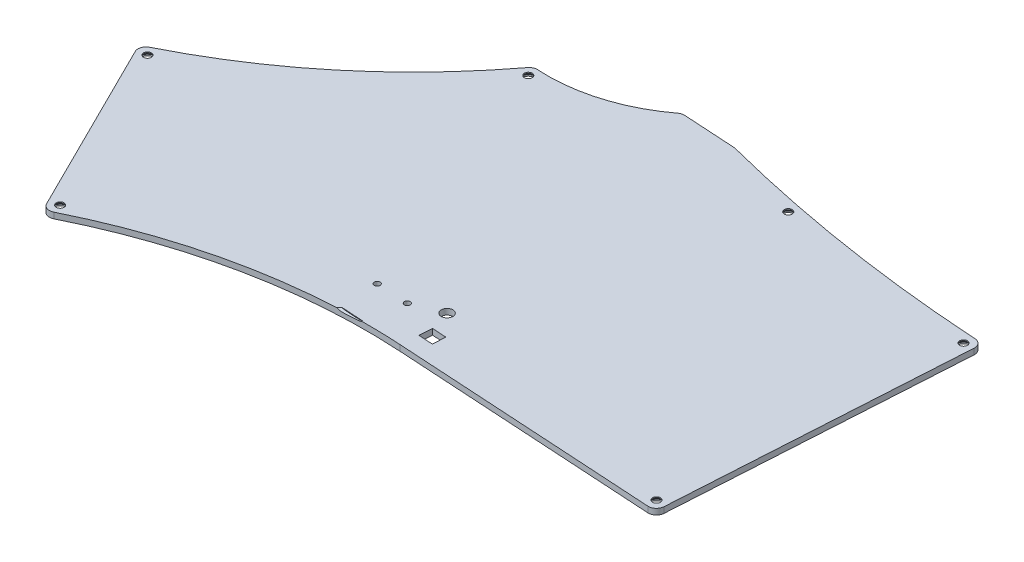
SolidWorks part; units mm, degrees
ref_plane "Front Plane" through (0, 0, 0) normal (0, 0, 1) x (1, 0, 0)
ref_plane "Top Plane" through (0, 0, 0) normal (0, 1, 0) x (1, 0, 0)
ref_plane "Right Plane" through (0, 0, 0) normal (1, 0, 0) x (0, 0, -1)
sketch "Main_line" plane through (0, 0, 0) normal (0, 1, 0) x (1, 0, 0)
  line L0 (47.5657, -117.8094) -> (51.8578, -118.0699) construction
  line L9 (47.2541, -117.9909) -> (52.1451, -118.2877) construction
  line L10 (47.2541, -117.9909) -> (47.5207, -113.5989) construction
  line L11 (47.5207, -113.5989) -> (52.4117, -113.8958) construction
  line L12 (52.1451, -118.2877) -> (52.4117, -113.8958) construction
  line L13 (47.2541, -117.9909) -> (52.4117, -113.8958) construction
  line L14 (47.5207, -113.5989) -> (52.1451, -118.2877) construction
  line L15 (51.9637, -117.9762) -> (52.1939, -114.1831) construction
  line L16 (52.1001, -114.0773) -> (47.808, -113.8168) construction
  line L17 (47.7022, -113.9105) -> (47.472, -117.7035) construction
  line L57 (46.7162, -124.1696) -> (137.2622, -129.6653)
  line L58 (-85.9719, -82.3907) -> (-55.9349, -142.8392)
  line L59 (45.4717, -7.8806) -> (27.5047, -6.7901)
  line L60 (140.4384, -126.8525) -> (146.527, -26.5371)
  line L61 (46.7162, -124.1696) -> (137.2622, -129.6653) construction
  line L62 (-85.9719, -82.3907) -> (-55.9349, -142.8392) construction
  line L63 (45.4717, -7.8806) -> (27.5047, -6.7901) construction
  line L64 (140.4384, -126.8525) -> (146.527, -26.5371) construction
  circle A0 centre (45.4932, -106.5632) radius 1.5 construction
  circle A1 centre (35.7393, -110.4594) radius 1 construction
  circle A2 centre (24.7595, -109.793) radius 1 construction
  circle A3 centre (-11.2177, -21.9715) radius 1.35 construction
  circle A5 centre (45.4932, -106.5632) radius 1.5 construction
  circle A18 centre (-82.6154, -81.2804) radius 1.35 construction
  arc A121 (137.2622, -129.6653) -> (140.4384, -126.8525) centre (137.444, -126.6708) ccw
  arc A122 (46.7162, -124.1696) -> (-51.9133, -144.1909) centre (34.8975, -318.8948) ccw
  arc A123 (-55.9349, -142.8392) -> (-51.9133, -144.1909) centre (-53.2483, -141.5043) ccw
  arc A124 (-84.6203, -78.3691) -> (-85.9719, -82.3907) centre (-83.2853, -81.0557) ccw
  arc A125 (-84.6203, -78.3691) -> (-13.8495, -19.649) centre (-173.8216, 101.1455) ccw
  arc A126 (-11.2736, -18.4623) -> (-13.8495, -19.649) centre (-11.4554, -21.4568) ccw
  arc A127 (-11.2736, -18.4623) -> (25.5185, -7.388) centre (-7.907, 37.0071) ccw
  arc A128 (27.5047, -6.7901) -> (25.5185, -7.388) centre (27.323, -9.7846) ccw
  arc A129 (46.0378, -7.9698) -> (45.4717, -7.8806) centre (45.2899, -10.8751) ccw
  arc A130 (46.0378, -7.9698) -> (143.7143, -23.3609) centre (175.0715, 493.2805) ccw
  arc A131 (146.527, -26.5371) -> (143.7143, -23.3609) centre (143.5325, -26.3554) ccw
  arc A132 (137.2622, -129.6653) -> (140.4384, -126.8525) centre (137.444, -126.6708) ccw construction
  arc A133 (46.7162, -124.1696) -> (-51.9133, -144.1909) centre (34.8975, -318.8948) ccw construction
  arc A134 (-55.9349, -142.8392) -> (-51.9133, -144.1909) centre (-53.2483, -141.5043) ccw construction
  circle A146 centre (136.9752, -126.1414) radius 1.35 construction
  circle A149 centre (-53.0228, -140.8346) radius 1.35 construction
  circle A150 centre (-82.6154, -81.2804) radius 1.35 construction
  circle A151 centre (-11.2177, -21.9715) radius 1.35 construction
  circle A152 centre (73.917, -17.8993) radius 1.35 construction
  circle A153 centre (143.0032, -26.8239) radius 1.35 construction
  arc A154 (-84.6203, -78.3691) -> (-85.9719, -82.3907) centre (-83.2853, -81.0557) ccw construction
  arc A155 (-84.6203, -78.3691) -> (-13.8495, -19.649) centre (-173.8216, 101.1455) ccw construction
  arc A156 (-11.2736, -18.4623) -> (-13.8495, -19.649) centre (-11.4554, -21.4568) ccw construction
  arc A157 (-11.2736, -18.4623) -> (25.5185, -7.388) centre (-7.907, 37.0071) ccw construction
  arc A158 (27.5047, -6.7901) -> (25.5185, -7.388) centre (27.323, -9.7846) ccw construction
  arc A159 (46.0378, -7.9698) -> (45.4717, -7.8806) centre (45.2899, -10.8751) ccw construction
  arc A160 (46.0378, -7.9698) -> (143.7143, -23.3609) centre (175.0715, 493.2805) ccw construction
  arc A161 (146.527, -26.5371) -> (143.7143, -23.3609) centre (143.5325, -26.3554) ccw construction
  point P23 (49.8329, -115.9433)
  dimension "D2" = 2
  dimension "D3" = 0.2
  dimension "D4" = 3
  dimension "D5" = 0.2
  dimension "D6" = 0.2
  dimension "D7" = 0.2
  dimension "D1" = 0
sketch "Sketch1" plane through (0, 0, 0) normal (0, 1, 0) x (1, 0, 0)
  line L0 (47.5207, -113.5989) -> (52.4117, -113.8958)
  line L1 (47.5207, -113.5989) -> (47.2541, -117.9909)
  line L2 (52.4117, -113.8958) -> (52.1451, -118.2877)
  line L3 (47.2541, -117.9909) -> (52.1451, -118.2877)
  line L33 (-85.7928, -82.3017) -> (-55.7558, -142.7502)
  line L34 (46.7283, -123.97) -> (137.2743, -129.4656)
  line L35 (140.2388, -126.8404) -> (146.3274, -26.525)
  line L36 (45.4595, -8.0803) -> (27.4926, -6.9898)
  line L37 (-85.7928, -82.3017) -> (-55.7558, -142.7502)
  line L38 (46.7283, -123.97) -> (137.2743, -129.4656)
  line L39 (140.2388, -126.8404) -> (146.3274, -26.525)
  line L40 (45.4595, -8.0803) -> (27.4926, -6.9898)
  circle A2 centre (-53.0228, -140.8346) radius 1.35 construction
  circle A3 centre (24.7595, -109.793) radius 1
  circle A4 centre (35.7393, -110.4594) radius 1
  circle A5 centre (45.4932, -106.5632) radius 2
  circle A7 centre (35.7393, -110.4594) radius 1 construction
  circle A8 centre (24.7595, -109.793) radius 1 construction
  circle A93 centre (143.0032, -26.8239) radius 1.35
  circle A94 centre (143.0032, -26.8239) radius 1.35 construction
  circle A95 centre (73.917, -17.8993) radius 1.35
  circle A96 centre (-11.2177, -21.9715) radius 1.35
  circle A97 centre (-82.6154, -81.2804) radius 1.35
  circle A98 centre (-53.0228, -140.8346) radius 1.35
  circle A100 centre (136.9752, -126.1414) radius 1.35
  arc A139 (-84.5313, -78.5482) -> (-85.7928, -82.3017) centre (-83.2853, -81.0557) ccw
  arc A140 (-55.7558, -142.7502) -> (-52.0023, -144.0118) centre (-53.2483, -141.5043) ccw
  arc A141 (46.7283, -123.97) -> (-52.0023, -144.0118) centre (34.8975, -318.8948) ccw
  arc A142 (137.2743, -129.4656) -> (140.2388, -126.8404) centre (137.444, -126.6708) ccw
  arc A143 (146.3274, -26.525) -> (143.7022, -23.5605) centre (143.5325, -26.3554) ccw
  arc A144 (45.9879, -8.1635) -> (143.7022, -23.5605) centre (175.0715, 493.2805) ccw
  arc A145 (45.9879, -8.1635) -> (45.4595, -8.0803) centre (45.2899, -10.8751) ccw
  arc A146 (27.4926, -6.9898) -> (25.6388, -7.5477) centre (27.323, -9.7846) ccw
  arc A147 (-11.2858, -18.6619) -> (25.6388, -7.5477) centre (-7.907, 37.0071) ccw
  arc A148 (-11.2858, -18.6619) -> (-13.6899, -19.7695) centre (-11.4554, -21.4568) ccw
  arc A149 (-84.5313, -78.5482) -> (-13.6899, -19.7695) centre (-173.8216, 101.1455) ccw
  arc A150 (-84.5313, -78.5482) -> (-85.7928, -82.3017) centre (-83.2853, -81.0557) ccw
  arc A151 (-55.7558, -142.7502) -> (-52.0023, -144.0118) centre (-53.2483, -141.5043) ccw
  arc A152 (46.7283, -123.97) -> (-52.0023, -144.0118) centre (34.8975, -318.8948) ccw
  arc A153 (137.2743, -129.4656) -> (140.2388, -126.8404) centre (137.444, -126.6708) ccw
  arc A154 (146.3274, -26.525) -> (143.7022, -23.5605) centre (143.5325, -26.3554) ccw
  arc A155 (45.9879, -8.1635) -> (143.7022, -23.5605) centre (175.0715, 493.2805) ccw
  arc A156 (45.9879, -8.1635) -> (45.4595, -8.0803) centre (45.2899, -10.8751) ccw
  arc A157 (27.4926, -6.9898) -> (25.6388, -7.5477) centre (27.323, -9.7846) ccw
  arc A158 (-11.2858, -18.6619) -> (25.6388, -7.5477) centre (-7.907, 37.0071) ccw
  arc A159 (-11.2858, -18.6619) -> (-13.6899, -19.7695) centre (-11.4554, -21.4568) ccw
  arc A160 (-84.5313, -78.5482) -> (-13.6899, -19.7695) centre (-173.8216, 101.1455) ccw
  point P21 (45.2899, -106.5632)
  dimension "D2" = 4
  dimension "D1" = 0.2
extrude "Main_plate" add sketch "Sketch1" along normal blind 2
sketch "Sketch2" plane through (0, 0, 0) normal (0, -1, 0) x (1, 0, 0)
  circle A0 centre (136.9752, 126.1414) radius 2.5
  circle A2 centre (-53.0228, 140.8346) radius 2.5
  circle A3 centre (-82.6154, 81.2804) radius 2.5
  circle A4 centre (-11.2177, 21.9715) radius 2.5
  circle A5 centre (73.917, 17.8993) radius 2.5
  circle A6 centre (143.0032, 26.8239) radius 2.5
  dimension "D1" = 5
extrude "Screw_holes" cut sketch "Sketch2" against normal blind 1.7
chamfer "Screw_holes_chamfer" distance 1.2 angle 45 6 edges at (143.0032, 1.7, 24.3239) (73.917, 1.7, 15.3993) (-11.2177, 1.7, 19.4715) (-82.6154, 1.7, 78.7804) (-53.0228, 1.7, 138.3346) (136.9752, 1.7, 123.6414)
ref_plane "Charge_port_plane1" through (-7.3373, 0, 120.8889) normal (-0.0606, 0, 0.9982) x (0.9982, 0, 0.0606)
ref_plane "Charge_port_plane2" through (-7.6402, 0, 125.8797) normal (-0.0606, 0, 0.9982) x (0.9982, 0, 0.0606)
sketch "Sketch3" plane through (-7.3373, 0, 120.8889) normal (-0.0606, 0, 0.9982) x (0.9982, 0, 0.0606)
  line L0 (34.4656, 5.5) -> (39.2656, 5.5) construction
  line L1 (34.4656, 9.25) -> (39.2656, 9.25)
  line L2 (34.4656, 1.75) -> (39.2656, 1.75)
  line L3 (-43.1822, 0) -> (54.1529, 0) construction
  line L4 (147.6656, 2) -> (147.6656, 0) construction
  arc A0 (34.4656, 9.25) -> (34.4656, 1.75) centre (34.4656, 5.5) ccw
  arc A1 (39.2656, 1.75) -> (39.2656, 9.25) centre (39.2656, 5.5) ccw
  point P2 (36.8656, 5.5)
  dimension "D1" = 4.8
  dimension "D2" = 5.5
  dimension "D3" = 110.8
  dimension "D4" = 7.5
sketch "Sketch4" plane through (-7.6402, 0, 125.8797) normal (-0.0606, 0, 0.9982) x (0.9982, 0, 0.0606)
  line L0 (34.4656, 5.5) -> (39.2656, 5.5) construction
  line L1 (34.4656, 10.75) -> (39.2656, 10.75)
  line L2 (34.4656, 0.25) -> (39.2656, 0.25)
  arc A0 (34.4656, 10.75) -> (34.4656, 0.25) centre (34.4656, 5.5) ccw
  arc A1 (39.2656, 0.25) -> (39.2656, 10.75) centre (39.2656, 5.5) ccw
  point P4 (36.8656, 5.5)
  dimension "D1" = 10.5
loft "Cut-Loft1" cut profiles "Sketch4", "Sketch3"
